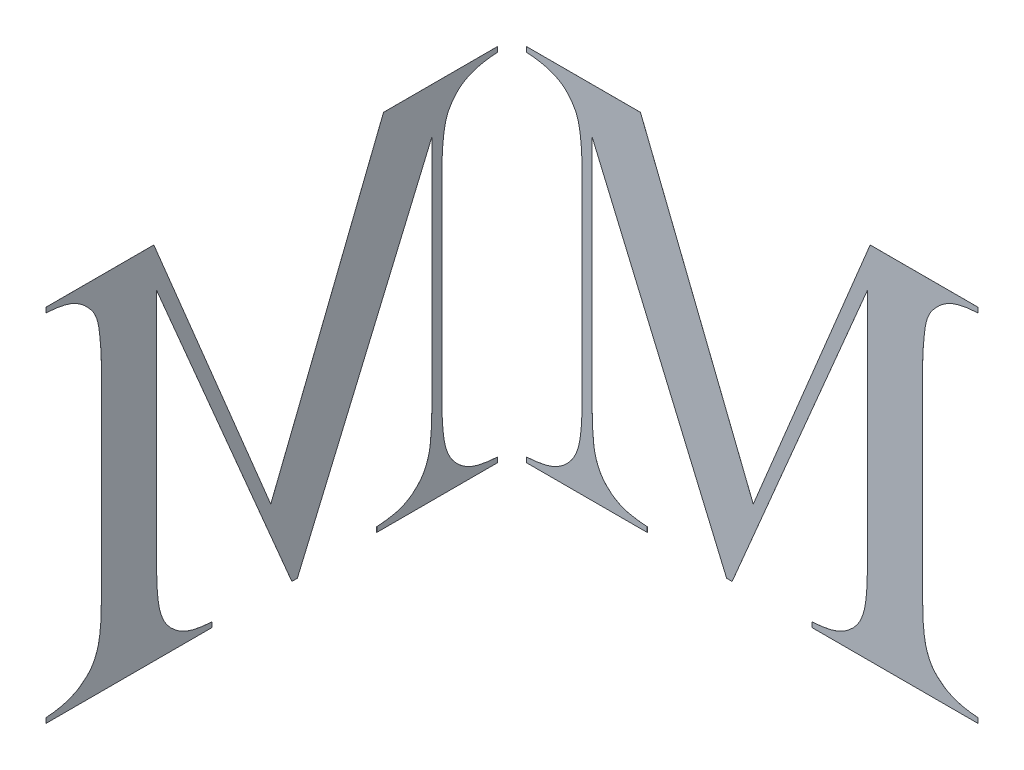
SolidWorks part; units mm, degrees
ref_plane "Front Plane" through (0, 0, 0) normal (0, 0, 1) x (1, 0, 0)
ref_plane "Top Plane" through (0, 0, 0) normal (0, 1, 0) x (1, 0, 0)
ref_plane "Right Plane" through (0, 0, 0) normal (1, 0, 0) x (0, 0, -1)
sketch "Sketch1" plane through (0, 0, 0) normal (0, 0, 1) x (1, 0, 0)
  line L0 (0, 0) -> (33.2544, 0) construction
  text T0 "M" font "Baskerville Old Face" height in points 72
ref_axis "Axis1" through (0, -0.943, 0) along (0, 1, 0)
extrude "Boss-Extrude2" add sketch "Sketch1" along normal blind 0.001
pattern_circular "CirPattern1" count 2 every 270 about axis through (0, -0.943, 0) along (0, 1, 0) of "Boss-Extrude2"
ref_plane "Plane1" through (0, 0, 0) normal (-0.7071, 0, 0.7071) x (0.7071, 0, 0.7071)
ref_axis "Axis2" through (0, 0, 0) along (-0.7071, 0, 0.7071)
ref_plane "Plane2" through (0, 0, 0) normal (-0.7071, 0, -0.7071) x (-0.7071, 0, 0.7071)
sketch "Sketch2" plane through (0, 0, 0.001) normal (0, 0, 1) x (1, 0, 0)
  line L0 (3.6699, 18.4919) -> (3.6699, 0)
  line L1 (0.7504, 18.4919) -> (6.5893, 18.4919) construction
  line L2 (6.9385, 0) -> (0.7504, 0) construction
  line L3 (3.6699, 9.2459) -> (-0.001, 9.2459)
  line L4 (-0.001, 14.2702) -> (-0.001, 4.2217) construction
  point P8 (3.6699, 9.2459)
ref_axis "Axis3" through (-0.001, 9.2459, 0.001) along (-0.7071, 0, 0.7071)
ref_plane "Plane3" through (2.1012, 1.0816, 2.1012) normal (-0.6645, -0.342, -0.6645) x (-0.7071, 0, 0.7071)
sketch "Sketch3" plane through (2.1012, 1.0816, 2.1012) normal (-0.6645, -0.342, -0.6645) x (-0.7071, 0, 0.7071)
  line L0 (-0.5306, 16.9539) -> (0.5313, 16.9541) construction
  line L1 (0.5313, 16.9541) -> (0.0004, 16.954) construction
  line L2 (0.0004, 16.954) -> (0.0004, -0.1814) construction
  line L4 (-0.5306, -0.1815) -> (0.5313, -0.1812) construction
  circle A1 centre (0.0004, 3.651) radius 21.8324
  point P8 (0.0004, 3.651)
  point P15 (0.0004, 8.3863)
  point P16 (0, 0)
  point P17 (0, 3.8224)
  point P18 (0, 3.651)
